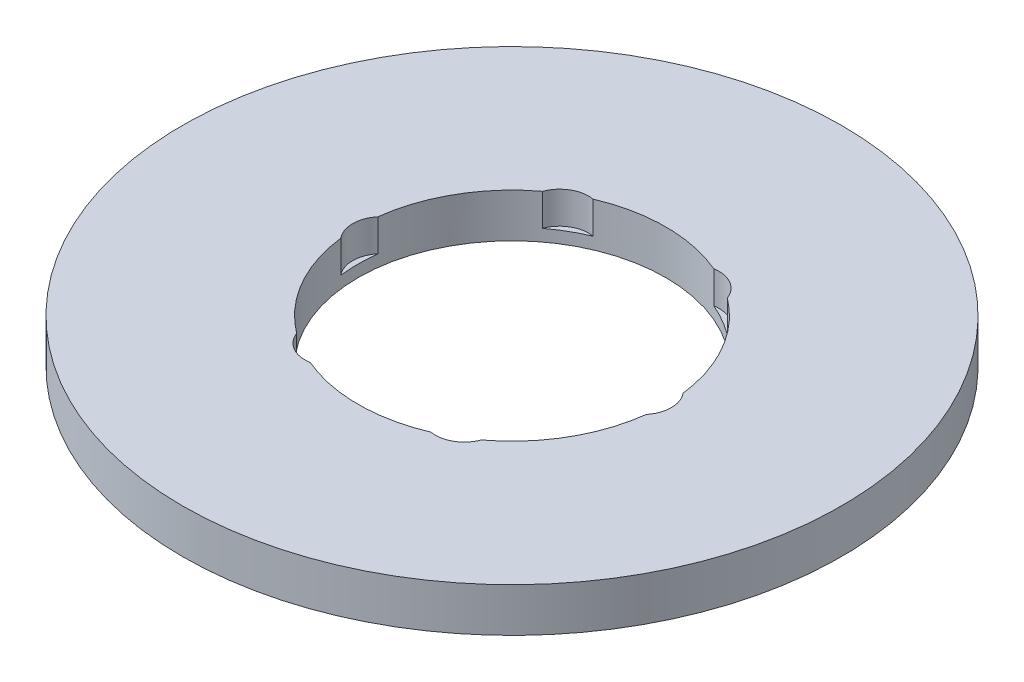
SolidWorks part; units mm, degrees
ref_plane "Front Plane" through (0, 0, 0) normal (0, 0, 1) x (1, 0, 0)
ref_plane "Top Plane" through (0, 0, 0) normal (0, 1, 0) x (1, 0, 0)
ref_plane "Right Plane" through (0, 0, 0) normal (1, 0, 0) x (0, 0, -1)
sketch "Sketch1" plane through (0, 0, 0) normal (0, 1, 0) x (1, 0, 0)
  circle A0 centre (0, 0) radius 37.5
  dimension "FLANGE_OD" = 75
extrude "Boss-Extrude1" add sketch "Sketch1" along normal blind 5
sketch "Sketch2" plane through (0, 0, 0) normal (0, 1, 0) x (1, 0, 0)
  circle A0 centre (0, 0) radius 17.5
  dimension "BORE_D" = 35
extrude "Cut-Extrude1" cut sketch "Sketch2" along normal through all
sketch "Sketch3" plane through (0, 5, 0) normal (0, 1, 0) x (1, 0, 0)
  circle A0 centre (0, 0) radius 14.8333 construction
  circle A1 centre (-14.8333, 0) radius 3.2984
  dimension "BOLT_D" = 6.5968
  dimension "BOLT_PCD" = 29.6666
extrude "Cut-Extrude2" cut sketch "Sketch3" against normal blind 3.6504
pattern_circular "CirPattern1" count 6 over 360 about axis through (0, 0, 0) along (0, 1, 0) of "Cut-Extrude2"
